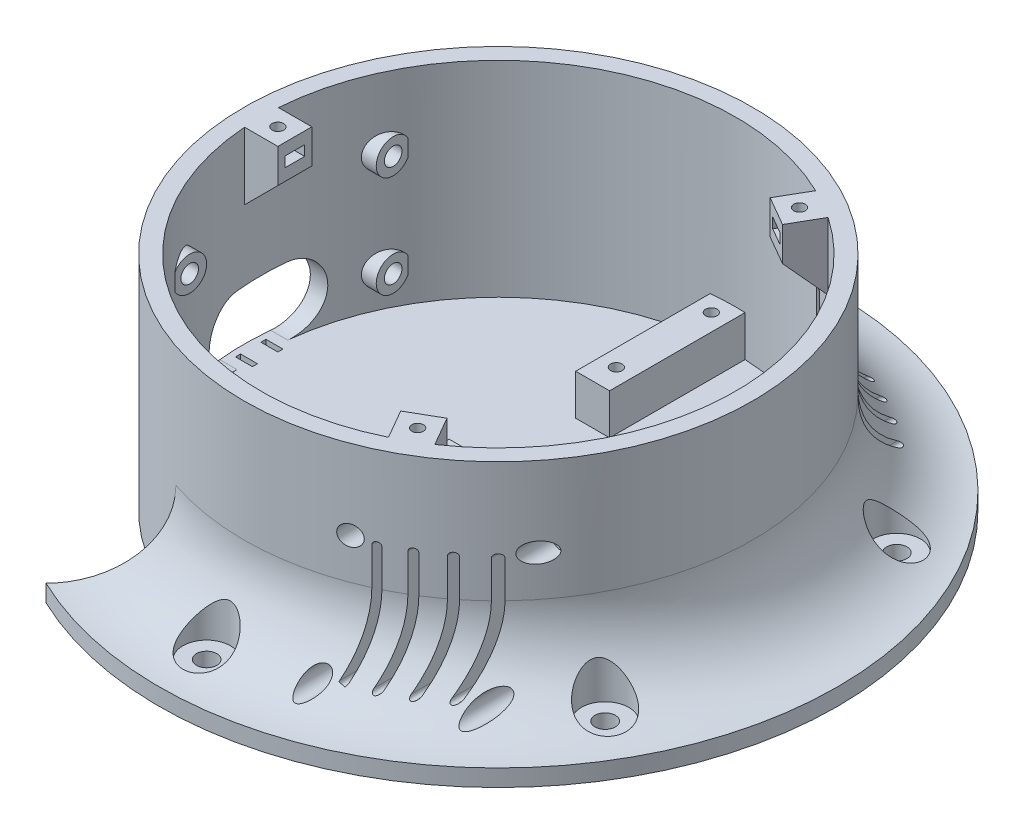
SolidWorks part; units mm, degrees
material "PLA"
ref_plane "Alzado" through (0, 0, 0) normal (0, 0, 1) x (1, 0, 0)
ref_plane "Planta" through (0, 0, 0) normal (0, 1, 0) x (1, 0, 0)
ref_plane "Vista lateral" through (0, 0, 0) normal (1, 0, 0) x (0, 0, -1)
sketch "Croquis1" plane through (0, 0, 0) normal (0, 0, 1) x (1, 0, 0)
  line L0 (0, 5) -> (0, 0)
  line L1 (0, 0) -> (100, 0)
  line L2 (100, 0) -> (100, 5)
  line L5 (75, 65.5) -> (70, 65.5)
  line L6 (70, 65.5) -> (70, 5)
  line L7 (70, 5) -> (0, 5)
  line L8 (0, 78.0387) -> (0, -48.9412) construction
  line L9 (75, 65.5) -> (75, 30)
  arc A0 (75, 30) -> (100, 5) centre (100, 30) ccw
  point P11 (100, 2.5)
  dimension "D6" = 50
  dimension "D1" = 65.5
  dimension "D2" = 70
  dimension "D3" = 75
  dimension "D4" = 100
  dimension "D5" = 5
  dimension "D7" = 5
  dimension "D8" = 35.5
revolve "Revolución1" add sketch "Croquis1" angle 360 about L8
sketch "Croquis2" plane through (0, 65.5, 0) normal (0, 1, 0) x (1, 0, 0)
  line L0 (-112.9437, 100) -> (-112.9437, -100)
  line L1 (-112.9437, 100) -> (-52.9437, 100)
  line L2 (-52.9437, 100) -> (-24, 71.0563)
  line L3 (-112.9437, -100) -> (-52.9437, -100)
  line L4 (-52.9437, -100) -> (-24, -71.0563)
  arc A0 (-24, 71.0563) -> (-24, -71.0563) centre (0, 0) ccw
  circle A1 centre (0, 0) radius 75 construction
  point P5 (-112.9437, 0)
  dimension "D1" = 200
  dimension "D2" = 60
  dimension "D3" = 135
  dimension "D4" = 24
extrude "Cortar-Extruir1" cut sketch "Croquis2" against normal blind 109
sketch "Croquis3" plane through (0, 0, 0) normal (0, 0, 1) x (1, 0, 0)
  line L0 (-72, 65.5) -> (-72, 43.5)
  line L2 (-72, 43.5) -> (-60, 55.5)
  line L3 (-60, 55.5) -> (-60, 65.5)
  line L4 (75, 65.5) -> (-75, 65.5) construction
  line L6 (-60, 65.5) -> (-70, 65.5)
  line L7 (-70, 65.5) -> (-72, 65.5)
  dimension "D1" = 10
  dimension "D2" = 45
  dimension "D3" = 10
  dimension "D4" = 2
  dimension "D5" = 70
extrude "Saliente-Extruir1" add sketch "Croquis3" along normal blind 5 and the other way blind 5
sketch "Croquis4" plane through (0, 65.5, 0) normal (0, 1, 0) x (1, 0, 0)
  line L0 (-60, 5) -> (-60, -5) construction
  circle A0 centre (-65, 0) radius 1.7
  point P6 (-60, 0)
  dimension "D2" = 3.4
  dimension "D1" = 5
extrude "Cortar-Extruir2" cut sketch "Croquis4" against normal blind 22
ref_plane "Plano1" through (0, 60.5, 0) normal (0, 1, 0) x (1, 0, 0)
sketch "Croquis5" plane through (0, 60.5, 0) normal (0, 1, 0) x (1, 0, 0)
  line L0 (-63.325, 2.9012) -> (-56.675, 2.9012)
  line L1 (-68.35, 0) -> (-66.675, -2.9012)
  line L2 (-66.675, -2.9012) -> (-63.325, -2.9012)
  line L5 (-63.325, 2.9012) -> (-66.675, 2.9012)
  line L6 (-66.675, 2.9012) -> (-68.35, 0)
  line L7 (-56.675, 2.9012) -> (-56.675, -2.9012)
  line L8 (-56.675, -2.9012) -> (-63.325, -2.9012)
  line L9 (-60, 5) -> (-69.8212, 5) construction
  line L10 (-61.65, 0) -> (-63.325, 2.9012) [skipped]
  line L11 (-62.4528, -1.3904) -> (-61.65, 0) [skipped]
  circle A0 centre (-65, 0) radius 3.35 construction
  dimension "D1" = 6.7
  dimension "D2" = 10
extrude "Cortar-Extruir3" cut sketch "Croquis5" against normal blind 1.5 and the other way blind 1.5
pattern_circular "MatrizC1" count 3 over 360 about axis through (0, 65.5, 0) along (0, 1, 0) of "Saliente-Extruir1", "Cortar-Extruir2", "Cortar-Extruir3"
sketch "Croquis6" plane through (0, 0, 0) normal (0, -1, 0) x (1, 0, 0)
  circle A0 centre (0, -86) radius 3
  dimension "D1" = 6
  dimension "D2" = 86
extrude "Cortar-Extruir4" cut sketch "Croquis6" against normal blind 30.35
ref_plane "Plano2" through (0, 20, 0) normal (0, -1, 0) x (-1, 0, 0)
sketch "Croquis7" plane through (0, 20, 0) normal (0, -1, 0) x (-1, 0, 0)
  circle A0 centre (0, 86) radius 7
  dimension "D1" = 14
extrude "Cortar-Extruir5" cut sketch "Croquis7" along normal blind 15
pattern_circular "MatrizC2" count 6 over 360 about axis through (0, 65.5, 0) along (0, 1, 0) of "Cortar-Extruir4", "Cortar-Extruir5"
sketch "Croquis8" plane through (0, 0, 0) normal (0, -1, 0) x (1, 0, 0)
  line L1 (24.5, -15.5) -> (55.5, -15.5) construction
  line L2 (24.5, -15.5) -> (24.5, 15.5) construction
  line L3 (24.5, 15.5) -> (55.5, 15.5) construction
  line L4 (55.5, -15.5) -> (55.5, 15.5) construction
  circle A0 centre (24.5, 15.5) radius 1.7
  circle A1 centre (55.5, 15.5) radius 1.7
  circle A2 centre (24.5, -15.5) radius 1.7
  circle A3 centre (55.5, -15.5) radius 1.7
  point P4 (24.5, 0)
  dimension "D4" = 3.4
  dimension "D1" = 31
  dimension "D2" = 31
  dimension "D3" = 24.5
extrude "Cortar-Extruir6" cut sketch "Croquis8" against normal blind 15
sketch "Croquis9" plane through (0, 0, 0) normal (0, -1, 0) x (1, 0, 0)
  circle A0 centre (24.5, 15.5) radius 2.95
  circle A1 centre (24.5, -15.5) radius 2.95
  circle A2 centre (55.5, -15.5) radius 2.95
  circle A3 centre (55.5, 15.5) radius 2.95
  dimension "D1" = 5.9
extrude "Cortar-Extruir7" cut sketch "Croquis9" against normal blind 2.5
sketch "Croquis10" plane through (0, 5, 0) normal (0, 1, 0) x (1, 0, 0)
  line L1 (2.8, 30) -> (-7.2, 30)
  line L2 (2.8, 30) -> (2.8, 69.944)
  line L4 (-7.2, 30) -> (-7.2, 69.6287)
  arc A0 (2.8, 69.944) -> (-7.2, 69.6287) centre (0, 0) ccw
  circle A1 centre (0, 0) radius 70 construction
  dimension "D1" = 30
  dimension "D2" = 2.8
  dimension "D3" = 10
extrude "Saliente-Extruir2" add sketch "Croquis10" along normal blind 12
sketch "Croquis11" plane through (0, 17, 0) normal (0, 1, 0) x (1, 0, 0)
  circle A0 centre (-2.2, 37) radius 1.7
  dimension "D3" = 3.4
  dimension "D1" = 5
  dimension "D2" = 7
extrude "Cortar-Extruir8" cut sketch "Croquis11" against normal blind 21
ref_plane "Plano3" through (0, 10.65, 0) normal (0, 1, 0) x (1, 0, 0)
sketch "Croquis12" plane through (0, 10.65, 0) normal (0, 1, 0) x (1, 0, 0)
  line L0 (-3.875, 39.9012) -> (-10.525, 39.9012)
  line L2 (-3.875, 34.0988) -> (-0.525, 34.0988)
  line L3 (-0.525, 34.0988) -> (1.15, 37)
  line L4 (1.15, 37) -> (-0.525, 39.9012)
  line L5 (-0.525, 39.9012) -> (-3.875, 39.9012)
  line L7 (-10.525, 39.9012) -> (-10.525, 34.0988)
  line L8 (-10.525, 34.0988) -> (-3.875, 34.0988)
  line L9 (-7.2, 30) -> (2.8, 30) construction
  line L10 (-5.55, 37) -> (-3.875, 34.0988) [skipped]
  line L11 (-3.875, 39.9012) -> (-5.55, 37) [skipped]
  line L12 (-7.2, 30) -> (2.8, 30) construction
  circle A0 centre (-2.2, 37) radius 3.35 construction
  dimension "D1" = 6.7
  dimension "D2" = 10
extrude "Cortar-Extruir9" cut sketch "Croquis12" against normal blind 3
pattern_linear "MatrizL1" count 2 spacing 28 along (0, 0, -1) of "Cortar-Extruir8", "Cortar-Extruir9"
sketch "Croquis13" plane through (0, 5, 0) normal (0, 1, 0) x (1, 0, 0)
  line L1 (63.5, -36) -> (21.5, -36)
  line L2 (63.5, -36) -> (63.5, -26)
  line L3 (63.5, -26) -> (21.5, -26)
  line L4 (21.5, -36) -> (21.5, -26)
  dimension "D1" = 10
  dimension "D2" = 42
  dimension "D3" = 36
  dimension "D4" = 21.5
extrude "Cortar-Extruir10" cut sketch "Croquis13" along normal blind 42
sketch "Croquis14" plane through (0, 5, 0) normal (0, 1, 0) x (1, 0, 0)
  line L0 (60.0333, -36) -> (21.5, -36)
  line L1 (21.5, -36) -> (21.5, -66.6164)
  circle A0 centre (0, 0) radius 70
  arc A1 (39.2407, -57.9669) -> (39.2407, 57.9669) centre (0, 0) ccw construction
  arc A2 (-7.2, 69.6287) -> (60.0333, -36) centre (0, 0) ccw construction
  arc M4 (-7.2, 69.6287) -> (60.0333, -36) centre (0, 0) ccw
  dimension "D1" = 42
extrude "Saliente-Extruir3" add sketch "Croquis14" along normal blind 42 contours L0 L1 M4 region at (35.8526, 5, 47.5073)
sketch "Croquis15" plane through (0, 0, 36) normal (0, 0, -1) x (-1, 0, 0)
  line L0 (-53, 41) -> (-53, 11) construction
  line L1 (-32, 11) -> (-53, 11) construction
  line L2 (-32, 11) -> (-32, 41) construction
  line L3 (-32, 41) -> (-53, 41) construction
  line L4 (-53, 11) -> (-53, 41) construction
  line L5 (-32, 11) -> (-53, 41) construction
  line L6 (-32, 41) -> (-53, 11) construction
  line L7 (-52, 41) -> (-52, 11)
  line L8 (-54, 41) -> (-54, 11)
  line L9 (-32, 41) -> (-32, 11) construction
  line L10 (-31, 41) -> (-31, 11)
  line L11 (-33, 41) -> (-33, 11)
  line L12 (-46, 41) -> (-46, 11) construction
  line L13 (-45, 41) -> (-45, 11)
  line L14 (-47, 41) -> (-47, 11)
  line L15 (-39, 41) -> (-39, 11) construction
  line L16 (-38, 41) -> (-38, 11)
  line L17 (-40, 41) -> (-40, 11)
  arc A0 (-52, 41) -> (-54, 41) centre (-53, 41) ccw
  arc A1 (-54, 11) -> (-52, 11) centre (-53, 11) ccw
  arc A2 (-31, 41) -> (-33, 41) centre (-32, 41) ccw
  arc A3 (-33, 11) -> (-31, 11) centre (-32, 11) ccw
  arc A4 (-45, 41) -> (-47, 41) centre (-46, 41) ccw
  arc A5 (-47, 11) -> (-45, 11) centre (-46, 11) ccw
  arc A6 (-38, 41) -> (-40, 41) centre (-39, 41) ccw
  arc A7 (-40, 11) -> (-38, 11) centre (-39, 11) ccw
  point P0 (-42.5, 26)
  point P5 (-53, 26)
  point P12 (-32, 26)
  point P17 (-46, 26)
  point P24 (-39, 26)
  dimension "D7" = 1
  dimension "D1" = 30
  dimension "D2" = 7
  dimension "D3" = 21
  dimension "D4" = 21
  dimension "D5" = 7
  dimension "D6" = 7
extrude "Cortar-Extruir11" cut sketch "Croquis15" against normal blind 42 and the other way blind 129
sketch "Croquis16" plane through (0, 0, 36) normal (0, 0, -1) x (-1, 0, 0)
  line L7 (-26.5, 10) -> (-58.5, 10) construction
  line L8 (-26.5, 10) -> (-26.5, 42) construction
  line L9 (-26.5, 42) -> (-58.5, 42) construction
  line L10 (-58.5, 10) -> (-58.5, 42) construction
  line L11 (-26.5, 10) -> (-58.5, 42) construction
  line L12 (-26.5, 42) -> (-58.5, 10) construction
  circle A0 centre (-58.5, 42) radius 1.7
  circle A1 centre (-26.5, 42) radius 1.7
  circle A2 centre (-58.5, 10) radius 1.7
  circle A3 centre (-26.5, 10) radius 1.7
  point P5 (-42.5, 26)
  dimension "D5" = 3.4
  dimension "D1" = 21
  dimension "D2" = 21
  dimension "D3" = 32
  dimension "D4" = 32
extrude "Cortar-Extruir12" cut sketch "Croquis16" against normal blind 67
ref_plane "Plano4" through (0, 0, 101) normal (0, 0, -1) x (-1, 0, 0)
sketch "Croquis17" plane through (0, 0, 101) normal (0, 0, -1) x (-1, 0, 0)
  circle A0 centre (-26.5, 42) radius 2.95
  circle A1 centre (-26.5, 10) radius 2.95
  dimension "D1" = 5.9
extrude "Cortar-Extruir13" cut sketch "Croquis17" along normal blind 37
sketch "Croquis18" plane through (0, 0, 101) normal (0, 0, -1) x (-1, 0, 0)
  circle A0 centre (-58.5, 42) radius 2.95
  circle A1 centre (-58.5, 10) radius 2.95
  dimension "D1" = 5.9
extrude "Cortar-Extruir14" cut sketch "Croquis18" along normal blind 61
sketch "Croquis19" plane through (0, 0, 0) normal (1, 0, 0) x (0, 0, -1)
  line L0 (7.5, 15) -> (-7.5, 15) construction
  line L1 (7.5, 5) -> (-7.5, 5)
  line L2 (7.5, 25) -> (-7.5, 25)
  line L3 (-100, 0) -> (100, 0) construction
  arc A0 (7.5, 5) -> (7.5, 25) centre (7.5, 15) ccw
  arc A1 (-7.5, 25) -> (-7.5, 5) centre (-7.5, 15) ccw
  point P2 (0, 15)
  dimension "D2" = 10
  dimension "D1" = 15
  dimension "D3" = 5
extrude "Cortar-Extruir15" cut sketch "Croquis19" against normal blind 105
sketch "Croquis21" plane through (0, 5, 0) normal (0, 1, 0) x (1, 0, 0)
  line L1 (-73, 4.5) -> (-68, 4.5)
  line L2 (-73, 4.5) -> (-73, 3)
  line L3 (-73, 3) -> (-68, 3)
  line L4 (-68, 4.5) -> (-68, 3)
  line L5 (-73, 4.5) -> (-68, 3) construction
  line L6 (-73, 3) -> (-68, 4.5) construction
  line L7 (-73, -3) -> (-68, -3)
  line L8 (-73, -3) -> (-73, -4.5)
  line L9 (-73, -4.5) -> (-68, -4.5)
  line L10 (-68, -3) -> (-68, -4.5)
  line L11 (-73, -3) -> (-68, -4.5) construction
  line L12 (-73, -4.5) -> (-68, -3) construction
  point P0 (-70.5, 3.75)
  point P5 (-70.5, -3.75)
  dimension "D1" = 6
  dimension "D2" = 3
  dimension "D3" = 1.5
  dimension "D4" = 5
  dimension "D5" = 68
ref_plane "Plano6" through (-75, 0, 0) normal (-1, 0, 0) x (0, 0, 1)
sketch "Croquis22" plane through (-75, 0, 0) normal (-1, 0, 0) x (0, 0, 1)
  line L1 (30, 15) -> (-30, 15) construction
  line L2 (30, 15) -> (30, 45) construction
  line L3 (30, 45) -> (-30, 45) construction
  line L4 (-30, 15) -> (-30, 45) construction
  line L5 (30, 15) -> (-30, 45) construction
  line L6 (30, 45) -> (-30, 15) construction
  line L7 (-71.0563, 0) -> (71.0563, 0) construction
  circle A0 centre (-30, 45) radius 2.6
  circle A1 centre (-30, 15) radius 2.6
  circle A2 centre (30, 15) radius 2.6
  circle A3 centre (30, 45) radius 2.6
  point P0 (0, 30)
  point P10 (0, 0)
  dimension "D3" = 5.2
  dimension "D1" = 60
  dimension "D2" = 30
  dimension "D4" = 30
extrude "Cortar-Extruir16" cut sketch "Croquis22" against normal blind 14
ref_plane "Plano7" through (-61, 0, 0) normal (1, 0, 0) x (0, 0, -1)
sketch "Croquis23" plane through (-61, 0, 0) normal (1, 0, 0) x (0, 0, -1)
  circle A0 centre (-30, 45) radius 5
  circle A1 centre (-30, 15) radius 5
  circle A2 centre (30, 15) radius 5
  circle A3 centre (30, 45) radius 5
  circle A4 centre (30, 45) radius 2.6 construction
  circle A5 centre (30, 15) radius 2.6 construction
  circle A6 centre (-30, 15) radius 2.6 construction
  circle A7 centre (-30, 45) radius 2.6 construction
  circle A8 centre (30, 45) radius 2.6
  circle A9 centre (30, 15) radius 2.6
  circle A10 centre (-30, 15) radius 2.6
  circle A11 centre (-30, 45) radius 2.6
  dimension "D1" = 10
extrude "Saliente-Extruir4" add sketch "Croquis23" against normal up to surface (4.3835 mm away) up to face at (-61.9829, 44.3955, -32.5287)
extrude "Cortar-Extruir17" cut sketch "Croquis21" against normal blind 18
